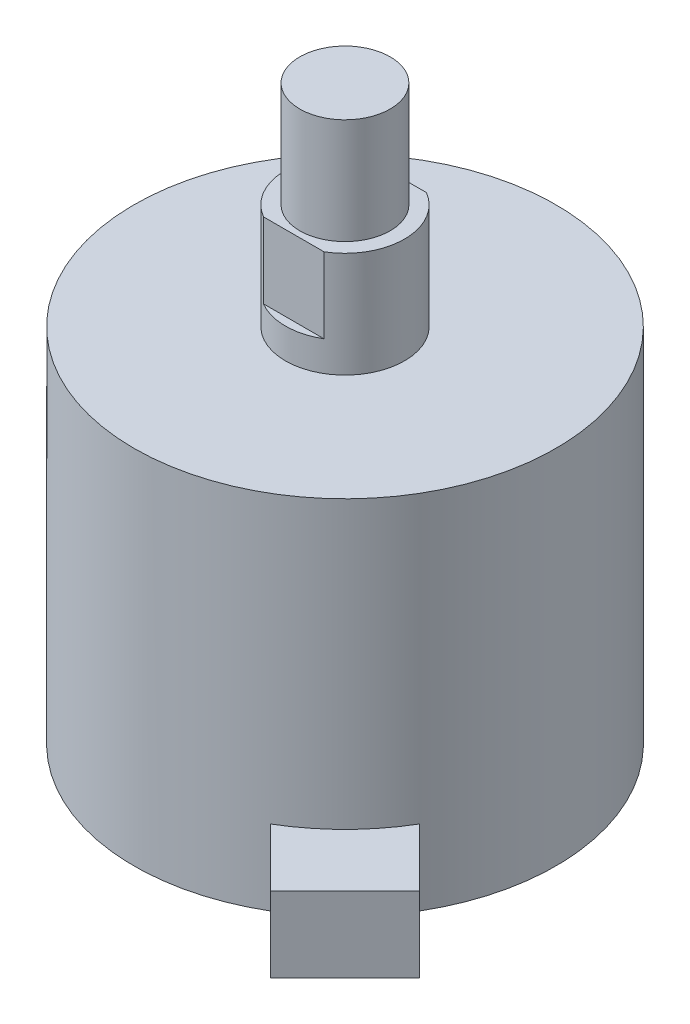
SolidWorks part; units mm, degrees
ref_plane "前视基准面" through (0, 0, 0) normal (0, 0, 1) x (1, 0, 0)
ref_plane "上视基准面" through (0, 0, 0) normal (0, 1, 0) x (1, 0, 0)
ref_plane "右视基准面" through (0, 0, 0) normal (1, 0, 0) x (0, 0, -1)
sketch "Sketch2" plane through (0, 0, 0) normal (0, 1, 0) x (1, 0, 0)
  circle A0 centre (0, 0) radius 14
  dimension "D1" = 28
extrude "Boss-Extrude1" add sketch "Sketch2" along normal blind 24
sketch "Sketch3" plane through (0, 24, 0) normal (0, 1, 0) x (1, 0, 0)
  circle A0 centre (0, 0) radius 3.95
  dimension "D1" = 7.9
extrude "Boss-Extrude2" add sketch "Sketch3" along normal blind 7
sketch "Sketch4" plane through (0, 31, 0) normal (0, 1, 0) x (1, 0, 0)
  circle A0 centre (0, 0) radius 3
  dimension "D1" = 6
extrude "Boss-Extrude3" add sketch "Sketch4" along normal blind 7
sketch "Sketch6" plane through (0, 0, 0) normal (0, -1, 0) x (1, 0, 0)
  line L0 (0, 0) -> (9.25, 0) construction
  circle A0 centre (9.25, 0) radius 1.5
  circle A1 centre (-9.25, 0) radius 1.5
  circle A4 centre (0, 7.75) radius 1.5
  circle A5 centre (0, -7.75) radius 1.5
  point P10 (0, 0)
  point P11 (0, 0)
  point P13 (0, 0)
  point P15 (-3.165, -3.1579)
  dimension "D2" = 3
  dimension "D1" = 9.25
  dimension "D4" = 7.75
  dimension "D5" = 15.5
  dimension "D3" = 2
extrude "Cut-Extrude1" cut sketch "Sketch6" against normal blind 5
sketch "草图1" plane through (0, 0, 0) normal (0, -1, 0) x (1, 0, 0)
  circle A0 centre (0, 0) radius 3
  dimension "D1" = 6
extrude "凸台-拉伸1" add sketch "草图1" along normal blind 3
sketch "Sketch7" plane through (0, 31, 0) normal (0, 1, 0) x (1, 0, 0)
  line L0 (-2.0106, 3.4) -> (2.0106, 3.4)
  line L1 (-2.0106, -3.4) -> (2.0106, -3.4)
  line L2 (0, 0) -> (3.95, 0) construction
  circle A0 centre (0, 0) radius 3.95 construction
  circle A1 centre (0, 0) radius 3.95
  circle A4 centre (0, 0) radius 3.95 construction
  arc A5 (2.0106, 3.4) -> (-2.0106, 3.4) centre (0, 0) ccw
  arc A6 (-2.0106, -3.4) -> (2.0106, -3.4) centre (0, 0) ccw
  dimension "D2" = 6.8
  dimension "D1" = 0
extrude "Cut-Extrude2" cut sketch "Sketch7" against normal offset from surface (5 mm away) 2 up to face at (0, 24, 3.95)
ref_plane "Plane1" through (0, 0, 0) normal (-0.7071, 0, 0.7071) x (0.7071, 0, 0.7071)
sketch "Sketch8" plane through (0, 0, 0) normal (-0.7071, 0, 0.7071) x (0.7071, 0, 0.7071)
  line L0 (14, 0) -> (14, 24) construction
  line L1 (0, 0) -> (19, 0)
  line L2 (0, 0) -> (0, 5)
  line L3 (0, 5) -> (19, 5)
  line L4 (19, 0) -> (19, 5)
  dimension "D1" = 5
  dimension "D2" = 5
extrude "Boss-Extrude4" add sketch "Sketch8" along normal mid plane 7
equation "\"D4@Sketch6\"=\"D5@Sketch6\"/2"
